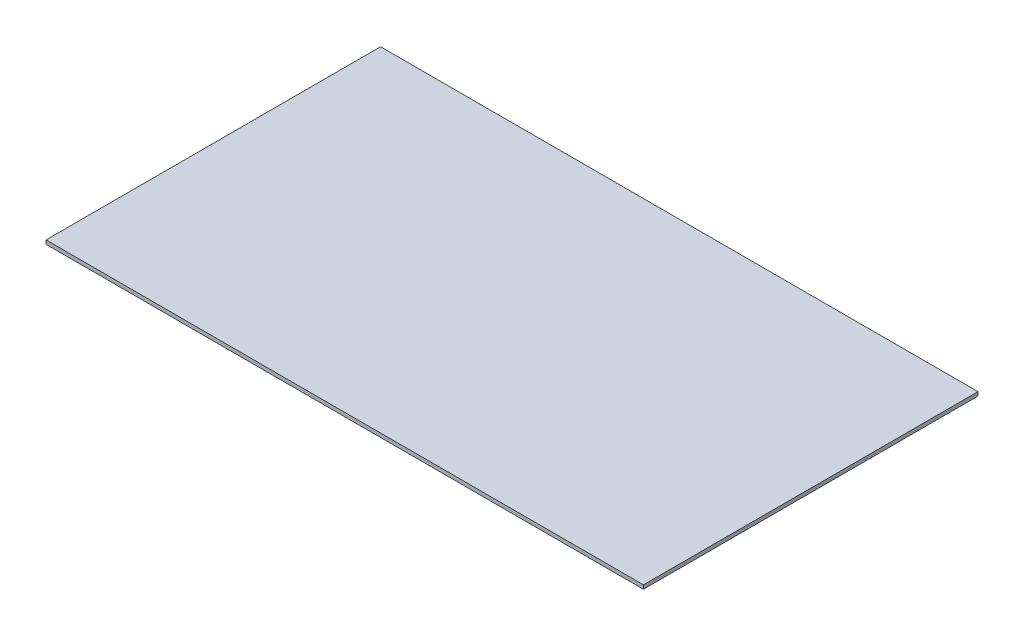
SolidWorks part; units mm, degrees
ref_plane "Front" through (0, 0, 0) normal (0, 0, 1) x (1, 0, 0)
ref_plane "Top" through (0, 0, 0) normal (0, 1, 0) x (1, 0, 0)
ref_plane "Right" through (0, 0, 0) normal (1, 0, 0) x (0, 0, -1)
sketch "Esquisse1" plane through (0, 0, 0) normal (0, 1, 0) x (1, 0, 0)
  line L1 (0, 0) -> (2500, 0)
  line L2 (0, 0) -> (0, 1400)
  line L3 (0, 1400) -> (2500, 1400)
  line L4 (2500, 0) -> (2500, 1400)
  dimension "D1" = 2500
  dimension "D2" = 1400
extrude "Boss.-Extru.1" add sketch "Esquisse1" along normal blind 16
